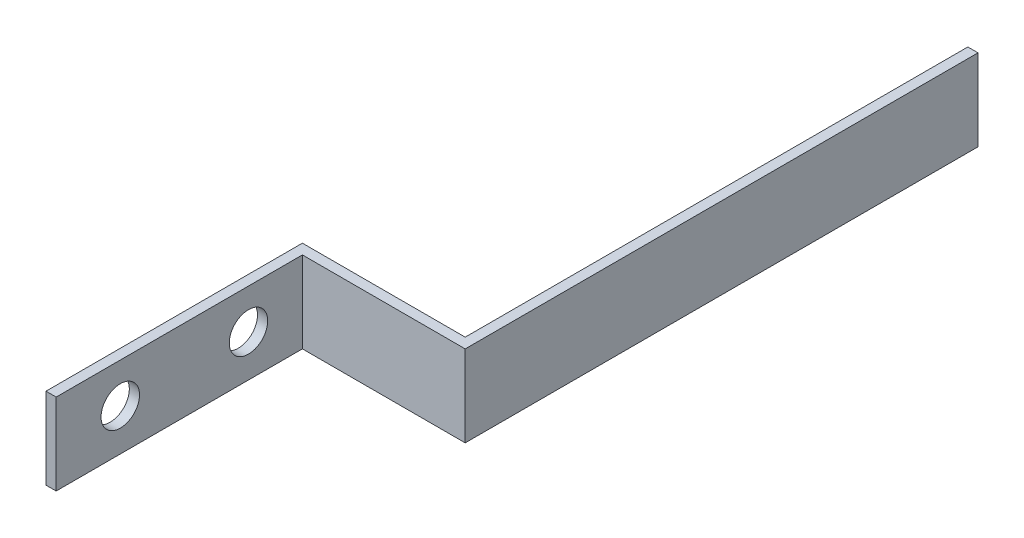
SolidWorks part; units mm, degrees
ref_plane "Front Plane" through (0, 0, 0) normal (0, 0, 1) x (1, 0, 0)
ref_plane "Top Plane" through (0, 0, 0) normal (0, 1, 0) x (1, 0, 0)
ref_plane "Right Plane" through (0, 0, 0) normal (1, 0, 0) x (0, 0, -1)
sketch "Sketch1" plane through (0, 0, 0) normal (0, 1, 0) x (1, 0, 0)
  line L0 (0, 0) -> (0, 80)
  line L1 (0, 80) -> (50.8, 80)
  line L2 (50.8, 80) -> (50.8, 236.825)
  line L3 (50.8, 236.825) -> (53.975, 236.825)
  line L4 (53.975, 236.825) -> (53.975, 76.825)
  line L5 (53.975, 76.825) -> (3.175, 76.825)
  line L6 (3.175, 76.825) -> (3.175, 0)
  line L7 (3.175, 0) -> (0, 0)
  dimension "D1" = 80
  dimension "D2" = 76.825
  dimension "D3" = 3.175
  dimension "D4" = 3.175
  dimension "D5" = 50.8
  dimension "D6" = 160
extrude "Boss-Extrude1" add sketch "Sketch1" along normal blind 25.4
sketch "Sketch2" plane through (3.175, 0, 0) normal (1, 0, 0) x (0, 0, -1)
  line L0 (20, 13) -> (60, 13)
  line L1 (0, 0) -> (20, 0)
  line L2 (0, 0) -> (0, 13)
  line L3 (0, 13) -> (20, 13)
  line L4 (20, 0) -> (20, 13)
  circle A0 centre (60, 13) radius 6
  circle A1 centre (20, 13) radius 6
  dimension "D1" = 13
  dimension "D2" = 20
  dimension "D3" = 40
extrude "Cut-Extrude1" cut sketch "Sketch2" against normal blind 25.4 contours A0 | A1
